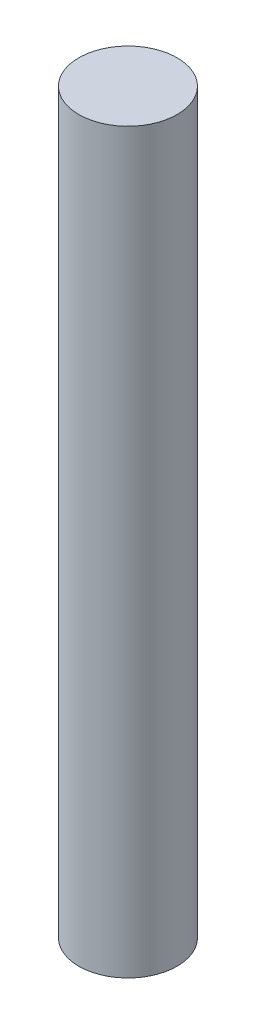
SolidWorks part; units mm, degrees
ref_plane "Front Plane" through (0, 0, 0) normal (0, 0, 1) x (1, 0, 0)
ref_plane "Top Plane" through (0, 0, 0) normal (0, 1, 0) x (1, 0, 0)
ref_plane "Right Plane" through (0, 0, 0) normal (1, 0, 0) x (0, 0, -1)
sketch "Sketch1" plane through (0, 0, 0) normal (0, 1, 0) x (1, 0, 0)
  circle A0 centre (0, 0) radius 4
  dimension "D1" = 8
extrude "Boss-Extrude1" add sketch "Sketch1" along normal blind 60
sketch "Sketch2" plane through (0, 60, 0) normal (0, 1, 0) x (1, 0, 0)
  circle A0 centre (0, 0) radius 4
curve "Helix/Spiral1" pitch 1 height 300 turns 300
sketch "Sketch3" plane through (0, 0, 0) normal (0, 0, 1) x (1, 0, 0)
  line L0 (-3.4587, 300.1288) -> (-3.9528, 300.3788)
  line L1 (-4.1997, 300.3788) -> (-4.1997, 299.6288)
  line L2 (-3.9527, 299.6288) -> (-3.4587, 299.8788)
  line L3 (-3.4587, 300.1288) -> (-3.4587, 299.8788)
  line L4 (-4, -700) -> (-4, 49300) construction
  line L5 (-4.1997, 299.6288) -> (-3.9527, 299.6288)
  line L6 (-4.1997, 300.3788) -> (-3.9528, 300.3788)
  point P2 (-4, 300.0038)
  point P7 (-4, 300.0038)
  dimension "D2" = 0.741
  dimension "D3" = 0.5413
  dimension "D4" = 0.25
sweep "Cut-Sweep4" [suppressed] cut profiles "Sketch3" path "Helix/Spiral1"
